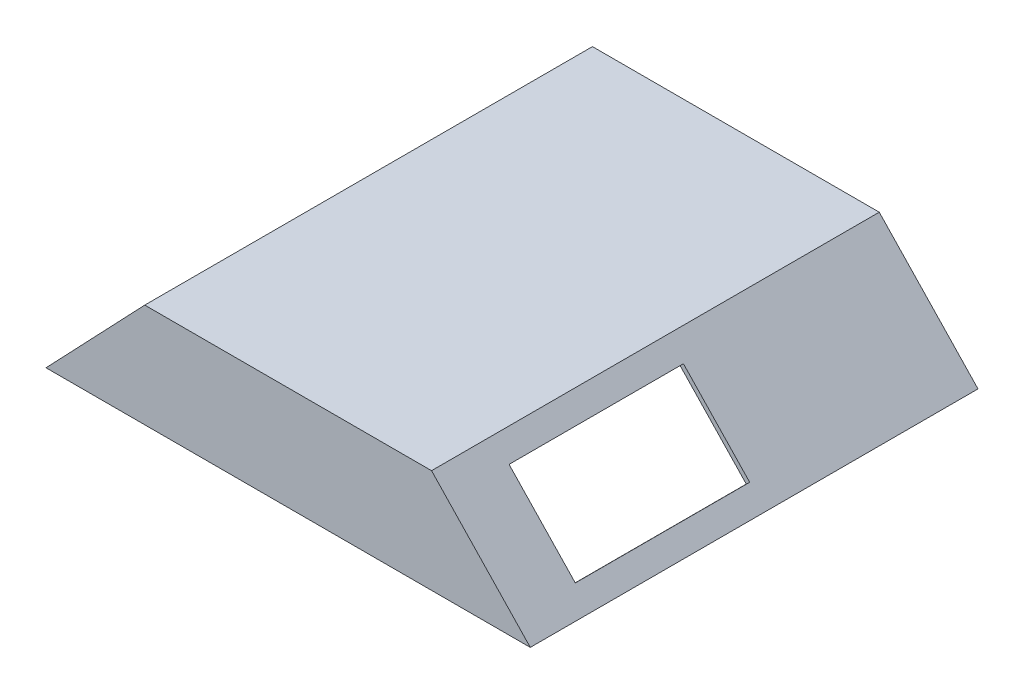
SolidWorks part; units mm, degrees
ref_plane "Alzado" through (0, 0, 0) normal (0, 0, 1) x (1, 0, 0)
ref_plane "Planta" through (0, 0, 0) normal (0, 1, 0) x (1, 0, 0)
ref_plane "Vista lateral" through (0, 0, 0) normal (1, 0, 0) x (0, 0, -1)
sketch "Croquis1" plane through (0, 0, 0) normal (0, 0, 1) x (1, 0, 0)
  line L0 (-50, 0) -> (-51.381, 0)
  line L1 (-51.381, 0) -> (-30.4286, 22)
  line L2 (-30, 21) -> (30, 21)
  line L3 (-30, 21) -> (-50, 0)
  line L4 (30.4286, 22) -> (-30.4286, 22)
  line L5 (0, 0) -> (0, 33.9502) construction
  line L6 (30, 21) -> (50, 0)
  line L7 (51.381, 0) -> (30.4286, 22)
  line L8 (50, 0) -> (51.381, 0)
  point P10 (0, 22)
  point P12 (0, 21)
  dimension "D1" = 1
  dimension "D2" = 30
  dimension "D3" = 50
  dimension "D4" = 1
  dimension "D5" = 21
extrude "Saliente-Extruir1" add sketch "Croquis1" along normal blind 94
sketch "Croquis3" plane through (26.9429, 25.6599, 0) normal (0.7241, 0.6897, 0) x (0, 0, -1)
  line L0 (-94, -5.0542) -> (0, -5.0542) construction
  line L1 (-82, -10.0542) -> (-45, -10.0542)
  line L2 (-82, -10.0542) -> (-82, -30.4351)
  line L3 (-82, -30.4351) -> (-45, -30.4351)
  line L4 (-45, -10.0542) -> (-45, -30.4351)
  line L5 (-94, -35.4351) -> (0, -35.4351) construction
  line L6 (-94, -35.4351) -> (-94, -5.0542) construction
  point P8 (-94, -20.2447)
  dimension "D1" = 5
  dimension "D2" = 37
  dimension "D3" = 5
  dimension "D4" = 12
extrude "Cortar-Extruir2" cut sketch "Croquis3" against normal up to next
sketch "Croquis4" plane through (0, 0, 94) normal (0, 0, 1) x (1, 0, 0)
  line L0 (-51.381, 0) -> (51.381, 0)
  line L1 (51.381, 0) -> (30.4286, 22)
  line L2 (30.4286, 22) -> (-30.4286, 22)
  line L3 (-30.4286, 22) -> (-51.381, 0)
extrude "Saliente-Extruir2" add sketch "Croquis4" along normal blind 1
